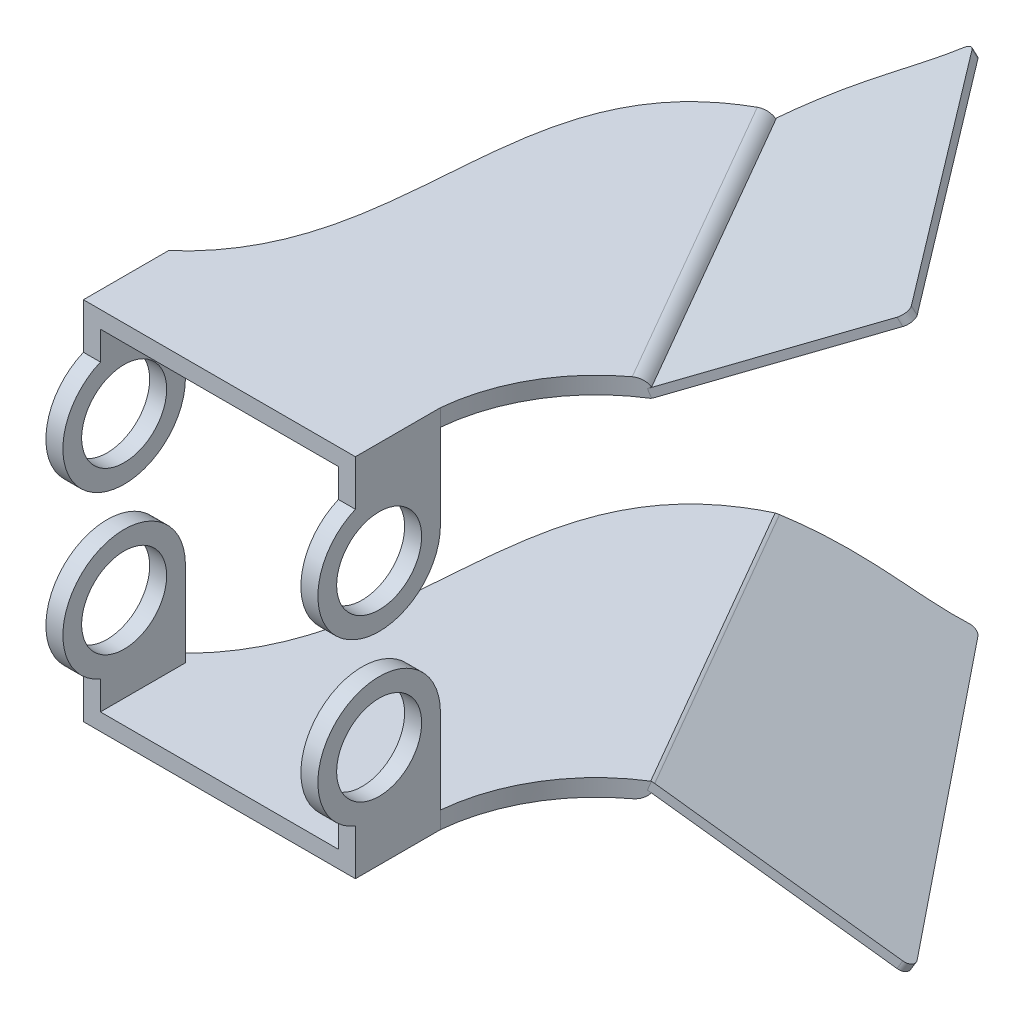
SolidWorks part; units mm, degrees
ref_plane "前视基准面" through (0, 0, 0) normal (0, 0, 1) x (1, 0, 0)
ref_plane "上视基准面" through (0, 0, 0) normal (0, 1, 0) x (1, 0, 0)
ref_plane "右视基准面" through (0, 0, 0) normal (1, 0, 0) x (0, 0, -1)
sketch "草图1" plane through (0, 0, 0) normal (0, 1, 0) x (1, 0, 0)
  line L0 (-33.2432, -24.9324) -> (-1.2432, -24.9324)
  line L2 (-1.2432, -24.9324) -> (-1.2432, -14.9324)
  line L3 (-33.2432, -24.9324) -> (-33.2432, -14.9324)
  line L4 (-11.7568, 35.0676) -> (8.2432, 0.4266)
  arc A1 (-1.2432, -14.9324) -> (8.2432, 0.4266) centre (18.9545, -16.7984) cw
  spline S0 degree 3 poles (-33.2432, -14.9324) (-17.5479, -1.0152) (-32.6261, 25.1651) (-11.7568, 35.0676) knots 0 0 0 0 1 1 1 1
  dimension "D2" = 10
  dimension "D1" = 10
  dimension "D4" = 40
  dimension "D6" = 32
extrude "凸台-拉伸1" add sketch "草图1" along normal blind 2 contours S0 L3 L0 L2 A1 L4
ref_plane "基准面1" through (-17.2432, 0, 0) normal (-1, 0, 0) x (0, 0, 1)
sketch "草图2" plane through (-17.2432, 0, 0) normal (-1, 0, 0) x (0, 0, 1)
  line L0 (14.9324, 2) -> (14.9324, 12)
  line L1 (24.9324, 2) -> (14.9324, 2) construction
  line L2 (19.9324, 0.7745) -> (19.9324, 8.1204) construction
  line L3 (24.9324, 2) -> (24.9324, 5.355)
  line L4 (14.9324, 2) -> (24.9324, 2)
  arc A0 (14.9324, 12) -> (24.9324, 5.355) centre (22.1402, 12) cw
  circle A1 centre (22.1402, 12) radius 5
  dimension "D3" = 10
  dimension "D1" = 10
  dimension "D2" = 5
extrude "凸台-拉伸2" add sketch "草图2" along normal mid plane 32
sketch "草图6" plane through (0, 0, 0) normal (0, 0, 1) x (1, 0, 0)
  line L0 (-31.2432, 19.4027) -> (-31.2432, 2)
  line L1 (-31.2432, 2) -> (-3.2432, 2)
  line L2 (-3.2432, 2) -> (-3.2432, 19.4027)
  line L3 (-3.2432, 19.4027) -> (-31.2432, 19.4027)
  line L4 (-33.2432, 19.2078) -> (-33.2432, 5.355) construction
  line L5 (-1.2432, 5.355) -> (-1.2432, 19.2078) construction
  line L6 (-33.2432, 0) -> (-1.2432, 0) construction
  dimension "D1" = 2
  dimension "D2" = 2
  dimension "D3" = 2
extrude "切除-拉伸1" cut sketch "草图6" along normal through all contours L3 L0 L1 L2
ref_plane "基准面2" through (2.3418, 4.6836, -1.352) normal (0.433, 0.866, -0.25) x (0.5, 0, 0.866)
sketch "草图7" plane through (2.3418, 4.6836, -1.352) normal (0.433, 0.866, -0.25) x (0.5, 0, 0.866)
  line L0 (-36.9948, 25.2143) -> (4.6842, 32.07)
  line L1 (5.8432, 31.002) -> (3.7522, 5.3671)
  line L4 (-36.2478, 5.3671) -> (-36.2532, 5.301)
  line L5 (-36.2532, 5.301) -> (3.7522, 5.301)
  line L6 (3.7522, 5.301) -> (3.7522, 5.3671)
  arc A0 (-37.8218, 24.0816) -> (-36.9948, 25.2143) centre (-36.8325, 24.2276) cw
  arc A1 (5.8432, 31.002) -> (4.6842, 32.07) centre (4.8465, 31.0833) ccw
  spline S0 degree 3 poles (-36.2478, 5.3671) (-38.6902, 13.7255) (-37.0648, 18.9511) (-37.8218, 24.0816) knots 0 0 0 0 0.951579 0.951579 0.951579 0.951579
  point P13 (5.9472, 32.2778)
  dimension "D3" = 1
  dimension "D1" = 1
  dimension "D2" = 27
extrude "凸台-拉伸3" add sketch "草图7" against normal blind 1
fillet "圆角2" radius 2 1 edges at (-1.7568, 0, -17.7471)
fillet "圆角3" radius 2 1 edges at (-1.8077, 2.0331, -17.7207)
sketch "草图8" plane through (0, 2, 0) normal (0, 1, 0) x (1, 0, 0)
  circle A0 centre (-15.7592, -7.5189) radius 5.8259
  dimension "D1" = 11.6519
extrude "凸台-拉伸4" add sketch "草图8" along normal blind 25
sketch "草图9" plane through (0, 0, 0) normal (0, 0, 1) x (1, 0, 0)
  line L0 (-21.5851, 27) -> (-9.9333, 27)
  line L1 (-9.9333, 27) -> (-9.9333, 2)
  line L2 (-9.9333, 2) -> (-21.5851, 2)
  line L3 (-21.5851, 2) -> (-21.5851, 27)
extrude "切除-拉伸2" cut sketch "草图9" along normal blind 22
sketch "草图10" plane through (-33.2432, 0, 0) normal (-1, 0, 0) x (0, 0, 1)
  line L0 (17.1402, 12) -> (27.1402, 12)
  line L1 (14.9324, 2) -> (-35.0346, 2) construction
  circle A0 centre (22.1402, 12) radius 5 construction
ref_plane "基准面3" through (0, 12, 0) normal (0, 1, 0) x (0, 0, 1)
ref_plane "基准面4" through (0, 21.5, 0) normal (0, 1, 0) x (0, 0, 1)
sketch "草图11" plane through (0, 2, 0) normal (0, 1, 0) x (1, 0, 0)
  circle A0 centre (-15.4374, -2.7065) radius 5.6642
extrude "凸台-拉伸5" add sketch "草图11" along normal blind 40
mirror "镜向1" about plane through (0, 21.5, 0) normal (0, 1, 0) of bodies 121
sketch "草图12" plane through (0, 0, 0) normal (0, 0, 1) x (1, 0, 0)
  line L0 (-21.1016, 41) -> (-9.7733, 41)
  line L1 (-31.2432, 41) -> (-3.2432, 41) construction
  line L2 (-21.1016, 41) -> (-9.7733, 41) construction
  line L3 (-9.7733, 41) -> (-9.7733, 2)
  line L4 (-9.7733, 2) -> (-21.1016, 2)
  line L5 (-21.1016, 2) -> (-21.1016, 41)
extrude "切除-拉伸3" cut sketch "草图12" along normal blind 20
extrude "切除-拉伸4" cut sketch "草图12<2>" against normal blind 10
sketch "草图12<2>" plane through (0, 0, 0) normal (0, 0, 1) x (1, 0, 0) same geometry as "草图12"
